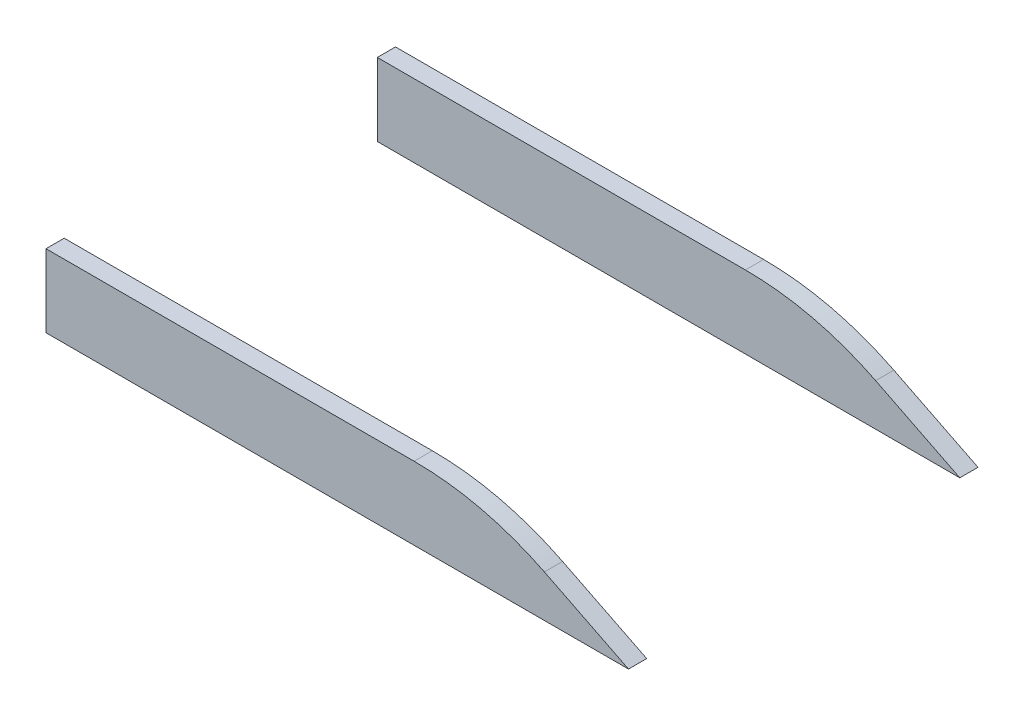
SolidWorks part; units mm, degrees
ref_plane "Front Plane" through (0, 0, 0) normal (0, 0, 1) x (1, 0, 0)
ref_plane "Top Plane" through (0, 0, 0) normal (0, 1, 0) x (1, 0, 0)
ref_plane "Right Plane" through (0, 0, 0) normal (1, 0, 0) x (0, 0, -1)
sketch "Sketch2" plane through (0, 0, 0) normal (0, 0, 1) x (1, 0, 0)
  line L0 (0, 0) -> (0, -20)
  line L1 (0, -20) -> (160, -20)
  line L2 (0, 0) -> (101.1146, 0)
  line L3 (136.8916, -8.4458) -> (160, -20)
  arc A1 (101.1146, 0) -> (136.8916, -8.4458) centre (101.1146, -80) cw
  point P12 (120, 0)
  dimension "D1" = 80
  dimension "D2" = 20
  dimension "D3" = 160
  dimension "D4" = 120
extrude "Boss-Extrude1" add sketch "Sketch2" along normal blind 5 from offset 91
extrude "Boss-Extrude2" add sketch "Sketch2<2>" along normal blind 5 separate body
sketch "Sketch2<2>" plane through (0, 0, 0) normal (0, 0, 1) x (1, 0, 0) same geometry as "Sketch2"
